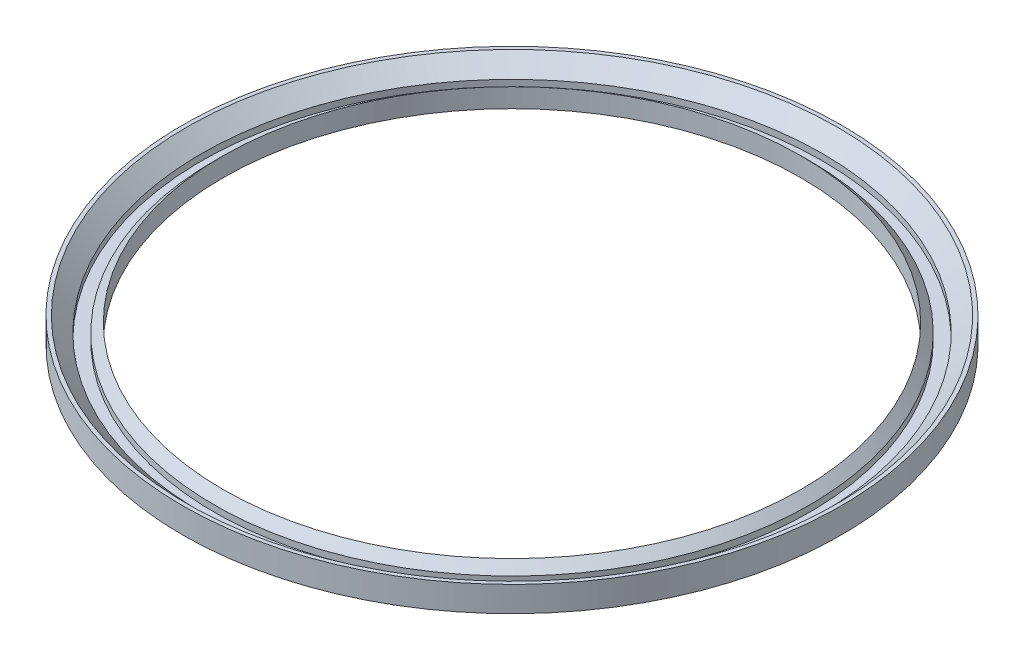
SolidWorks part; units mm, degrees
material "Stainless Steel (ferritic)"
ref_plane "Front Plane" through (0, 0, 0) normal (0, 0, 1) x (1, 0, 0)
ref_plane "Top Plane" through (0, 0, 0) normal (0, 1, 0) x (1, 0, 0)
ref_plane "Right Plane" through (0, 0, 0) normal (1, 0, 0) x (0, 0, -1)
sketch "Sketch1" plane through (0, 0, 0) normal (0, 0, 1) x (1, 0, 0)
  line L0 (0, -28.6657) -> (0, 30.2732) construction
  line L1 (0, 0) -> (73.9023, 0) construction
  line L2 (29.375, -1.4963) -> (27.8787, 0)
  line L3 (27.5, -2.5) -> (32.5, -2.5)
  line L4 (27.5, -2.5) -> (27.5, 2.5)
  line L5 (27.5, 2.5) -> (32.5, 2.5)
  line L6 (32.5, -2.5) -> (32.5, 2.5)
  line L7 (27.5, -2.5) -> (32.5, 2.5) construction
  line L8 (27.5, 2.5) -> (32.5, -2.5) construction
  line L9 (30.625, -1.4963) -> (32.1213, 0)
  line L10 (27.8787, 0) -> (29.375, 1.4963)
  line L11 (32.1213, 0) -> (30.625, 1.4963)
  line L12 (30, -2.1213) -> (30, 2.1213) construction
  line L13 (27.8787, 0) -> (32.1213, 0) construction
  line L14 (29.375, 1.4963) -> (29.375, 2.1213)
  line L15 (29.375, 2.1213) -> (30.625, 2.1213)
  line L16 (30.625, 2.1213) -> (30.625, 1.4963)
  line L17 (29.375, -1.4963) -> (29.375, -2.1213)
  line L18 (29.375, -2.1213) -> (30.625, -2.1213)
  line L19 (30.625, -2.1213) -> (30.625, -1.4963)
  circle A0 centre (30, 0) radius 1.5 construction
  point P5 (30, 0)
  dimension "D3" = 3
  dimension "D1" = 27.5
  dimension "D2" = 5
  dimension "D4" = 5
  dimension "D5" = 1.25
  dimension "D6" = 0.625
  dimension "D7" = 1.25
  dimension "D8" = 0.625
  dimension "D9" = 0.625
  dimension "D10" = 0.625
  dimension "D11" = 0.625
revolve "Revolve1" add sketch "Sketch1" angle 360 about L0
sketch "Sketch2" plane through (0, 0, 0) normal (0, 0, 1) x (1, 0, 0)
  line L0 (0, 0) -> (0, 27.7757) construction
  line L1 (0, 0) -> (94.5038, 0) construction
  line L2 (-32.5, -2.5) -> (32.5, -2.5) construction
  line L4 (28.5, 0) -> (32.5, 0)
  line L5 (27.5, 0) -> (27.5, 2.5)
  line L6 (27.5, 2.5) -> (32.5, 2.5)
  line L7 (32.5, 0) -> (32.5, 2.5)
  line L8 (27.5, 0) -> (27.5, -2.5)
  line L9 (27.5, -2.5) -> (28.5, -2.5)
  line L10 (28.5, 0) -> (28.5, -2.5)
  dimension "D1" = 2.5
  dimension "D2" = 27.5
  dimension "D3" = 5
  dimension "D4" = 2.5
  dimension "D5" = 1
revolve "Cut-Revolve1" cut sketch "Sketch2" angle 360 about L0
ref_axis "Axis1" through (0, 0.125, 0) along (0, -1, 0)
